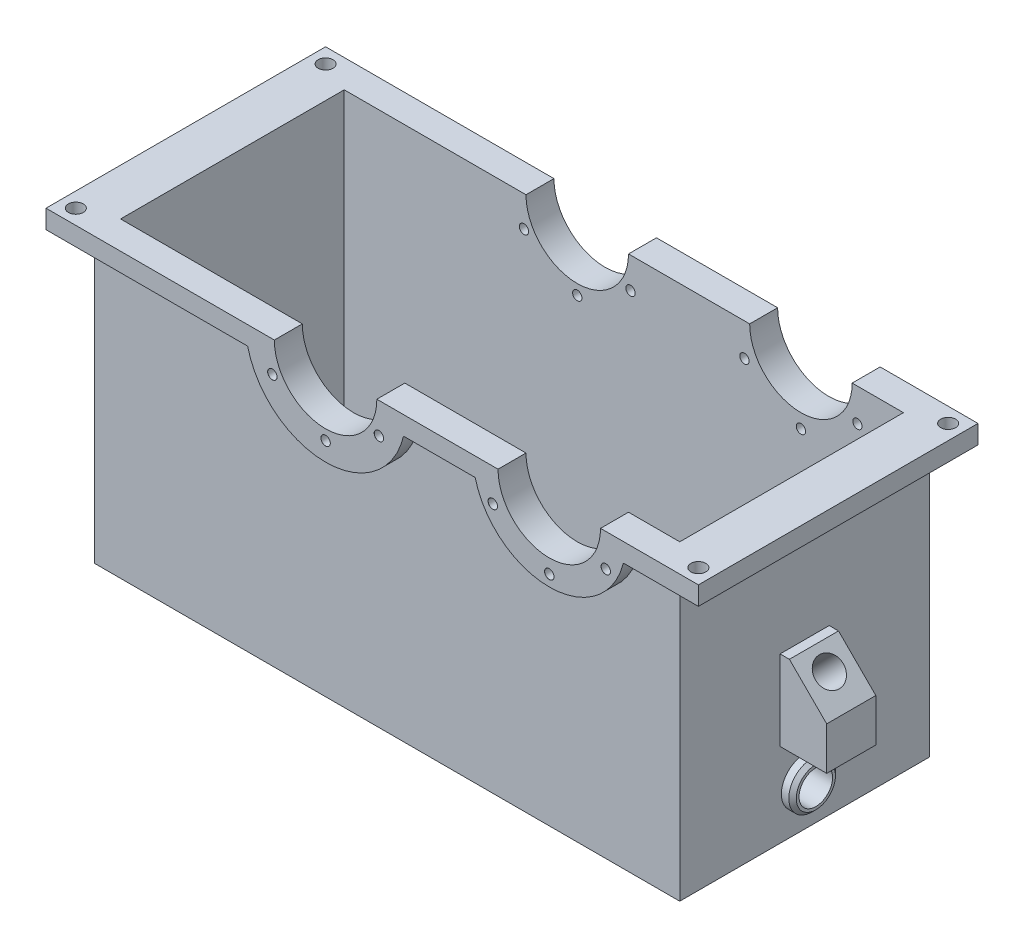
SolidWorks part; units mm, degrees
ref_plane "Front Plane" through (0, 0, 0) normal (0, 0, 1) x (1, 0, 0)
ref_plane "Top Plane" through (0, 0, 0) normal (0, 1, 0) x (1, 0, 0)
ref_plane "Right Plane" through (0, 0, 0) normal (1, 0, 0) x (0, 0, -1)
sketch "Sketch1" plane through (0, 0, 0) normal (0, 1, 0) x (1, 0, 0)
  line L1 (157, -67) -> (-157, -67)
  line L2 (157, -67) -> (157, 67)
  line L3 (157, 67) -> (-157, 67)
  line L4 (-157, -67) -> (-157, 67)
  line L5 (157, -67) -> (-157, 67) construction
  line L6 (157, 67) -> (-157, -67) construction
  point P0 (0, 0)
  dimension "D1" = 314
  dimension "D2" = 134
extrude "Boss-Extrude1" add sketch "Sketch1" along normal blind 160
sketch "Sketch2" plane through (0, 160, 0) normal (0, 1, 0) x (1, 0, 0)
  line L1 (175, -75) -> (-175, -75)
  line L2 (175, -75) -> (175, 75)
  line L3 (175, 75) -> (-175, 75)
  line L4 (-175, -75) -> (-175, 75)
  line L5 (175, -75) -> (-175, 75) construction
  line L6 (175, 75) -> (-175, -75) construction
  point P0 (0, 0)
  dimension "D1" = 350
  dimension "D2" = 150
extrude "Boss-Extrude3" add sketch "Sketch2" against normal blind 10
sketch "Sketch3" plane through (0, 0, 75) normal (0, 0, 1) x (1, 0, 0)
  line L0 (-175, 160) -> (175, 160) construction
  circle A0 centre (95, 160) radius 41
  circle A1 centre (95, 160) radius 27.5
  circle A2 centre (95, 160) radius 35 construction
  dimension "D2" = 82
  dimension "D3" = 55
  dimension "D4" = 70
  dimension "D1" = 80
extrude "Boss-Extrude5" add sketch "Sketch3" against normal through all contours A0
hole_wizard "Ø5.0mm Dowel Hole1" positions "Sketch4" profile "Sketch5" hole size "Ø5.0" standard "GB" end condition through all
sketch "Sketch4" plane through (0, 0, 75) normal (0, 0, 1) x (1, 0, 0)
  circle A0 centre (95, 160) radius 35 construction
  point P0 (95, 195)
sketch "Sketch5" plane through (95, 195, 75) normal (1, 0, 0) x (0, -1, 0)
  line L0 (0, 0) -> (0, 150)
  line L1 (0, 150) -> (2.5, 150)
  line L2 (2.5, 150) -> (2.5, 0.021)
  line L3 (2.5, 0.021) -> (2.525, 0)
  line L5 (2.525, 0) -> (0, 0)
  line L6 (-2.5, 0.021) -> (-2.525, 0) construction
  line L11 (0, -6.35) -> (0, 107.95) construction
  dimension "Thru Hole Dia." = 5
  dimension "Thru Hole Depth" = 150
  dimension "Near C'Sink Dia." = 5.05
  dimension "Near C'Sink Angle" = 100
pattern_circular "CirPattern1" count 6 over 360 about axis through (95, 160, -75) along (0, 0, 1) of "Ø5.0mm Dowel Hole1" reverse direction yes
extrude "Cut-Extrude1" cut sketch "Sketch3<3>" against normal through all contours A1
sketch "Sketch3<3>" plane through (0, 0, 75) normal (0, 0, 1) x (1, 0, 0) same geometry as "Sketch3"
sketch "Sketch6" plane through (0, 0, 75) normal (0, 0, 1) x (1, 0, 0)
  line L0 (-175, 160) -> (54, 160) construction
  circle A0 centre (-25, 160) radius 43
  circle A1 centre (-25, 160) radius 33 construction
  circle A2 centre (-25, 160) radius 27.5
  dimension "D2" = 86
  dimension "D3" = 55
  dimension "D4" = 66
  dimension "D1" = 120
extrude "Boss-Extrude6" add sketch "Sketch6" against normal through all contours A0
extrude "Cut-Extrude2" cut sketch "Sketch6<3>" against normal through all contours A2
sketch "Sketch6<3>" plane through (0, 0, 75) normal (0, 0, 1) x (1, 0, 0) same geometry as "Sketch6"
hole_wizard "Ø5.0mm Dowel Hole2" positions "Sketch7" profile "Sketch8" hole size "Ø5.0" standard "GB" end condition through all
sketch "Sketch7" plane through (0, 0, 75) normal (0, 0, 1) x (1, 0, 0)
  circle A0 centre (-25, 160) radius 33 construction
  point P0 (-25, 193)
sketch "Sketch8" plane through (-25, 193, 75) normal (1, 0, 0) x (0, -1, 0)
  line L0 (0, 0) -> (0, 150)
  line L1 (0, 150) -> (2.5, 150)
  line L2 (2.5, 150) -> (2.5, 0.021)
  line L3 (2.5, 0.021) -> (2.525, 0)
  line L5 (2.525, 0) -> (0, 0)
  line L6 (-2.5, 0.021) -> (-2.525, 0) construction
  line L11 (0, -6.35) -> (0, 107.95) construction
  dimension "Thru Hole Dia." = 5
  dimension "Thru Hole Depth" = 150
  dimension "Near C'Sink Dia." = 5.05
  dimension "Near C'Sink Angle" = 100
pattern_circular "CirPattern2" count 6 over 360 about axis through (-25, 160, -75) along (0, 0, 1) of "Ø5.0mm Dowel Hole2" reverse direction yes
mirror "Mirror1" about plane through (0, 0, 0) normal (0, 0, 1) of "CirPattern2"
mirror "Mirror2" about plane through (0, 0, 0) normal (0, 0, 1) of "CirPattern1"
sketch "Sketch9" plane through (157, 0, 0) normal (1, 0, 0) x (0, 0, -1)
  circle A0 centre (0, 22.5) radius 12.5
  circle A1 centre (0, 22.5) radius 9
  dimension "D2" = 25
  dimension "D3" = 18
  dimension "D1" = 22.5
extrude "Boss-Extrude7" add sketch "Sketch9" along normal blind 6 contours A0
extrude "Cut-Extrude3" cut sketch "Sketch9<3>" against normal blind 30 from offset 6 contours A1
sketch "Sketch9<3>" plane through (157, 0, 0) normal (1, 0, 0) x (0, 0, -1) same geometry as "Sketch9"
chamfer "Chamfer1" distance 2 angle 45 1 edges at (163, 22.5, -12.5)
sketch "Sketch10" plane through (157, 0, 0) normal (1, 0, 0) x (0, 0, -1)
  line L0 (0, 0) -> (0, 81.1635) construction
  line L1 (-13.175, 88) -> (13.175, 88)
  line L2 (-13.175, 88) -> (-13.175, 45)
  line L3 (-13.175, 45) -> (13.175, 45)
  line L4 (13.175, 88) -> (13.175, 45)
  line L5 (-67, 0) -> (67, 0) construction
  dimension "D1" = 45
  dimension "D2" = 43
  dimension "D3" = 26.35
extrude "Boss-Extrude8" add sketch "Sketch10" along normal blind 25
sketch "Sketch11" plane through (0, 0, -13.175) normal (0, 0, -1) x (-1, 0, 0)
  line L0 (-162, 88) -> (-182, 68)
  line L1 (-182, 88) -> (-157, 88) construction
  line L2 (-182, 45) -> (-182, 88) construction
  line L3 (-182, 45) -> (-157, 45) construction
  line L4 (-162, 88) -> (-183.7417, 106.3377)
  line L5 (-183.7417, 106.3377) -> (-200.6491, 72.8193)
  line L6 (-200.6491, 72.8193) -> (-182, 68)
  dimension "D1" = 5
  dimension "D2" = 23
extrude "Cut-Extrude4" cut sketch "Sketch11" against normal up to next
sketch "Sketch12" plane through (125, 125, 0) normal (0.7071, 0.7071, 0) x (0, 0, -1)
  circle A0 centre (0, -63.9932) radius 7.5
  dimension "D1" = 15
extrude "Cut-Extrude5" cut sketch "Sketch12" against normal blind 50
sketch "Sketch13" plane through (0, 160, 0) normal (0, 1, 0) x (1, 0, 0)
  line L0 (-175, 75) -> (-175, -75) construction
  line L1 (-68, 75) -> (-175, 75) construction
  circle A0 centre (-167, 67) radius 4
  dimension "D1" = 8
  dimension "D2" = 8
  dimension "D3" = 8
extrude "Cut-Extrude6" cut sketch "Sketch13" against normal through all both and the other way through all
mirror "Mirror3" about plane through (0, 0, 0) normal (1, 0, 0) of "Cut-Extrude6"
mirror "Mirror4" about plane through (0, 0, 0) normal (0, 0, 1) of "Cut-Extrude6"
mirror "Mirror5" about plane through (0, 0, 0) normal (0, 0, 1) of "Mirror3"
sketch "Sketch14" plane through (0, 0, 75) normal (0, 0, 1) x (1, 0, 0)
  line L1 (-175, 160) -> (189.1664, 160)
  line L2 (-175, 160) -> (-175, 252.8203)
  line L3 (-175, 252.8203) -> (189.1664, 252.8203)
  line L4 (189.1664, 160) -> (189.1664, 252.8203)
extrude "Cut-Extrude7" cut sketch "Sketch14" against normal through all
sketch "Sketch15" plane through (0, 160, 0) normal (0, 1, 0) x (1, 0, 0)
  line L1 (150, -60) -> (-150, -60)
  line L2 (150, -60) -> (150, 60)
  line L3 (150, 60) -> (-150, 60)
  line L4 (-150, -60) -> (-150, 60)
  line L5 (150, -60) -> (-150, 60) construction
  line L6 (150, 60) -> (-150, -60) construction
  point P0 (0, 0)
  dimension "D1" = 300
  dimension "D2" = 120
extrude "Cut-Extrude9" cut sketch "Sketch15" against normal offset from surface (150 mm away) 10 up to face at (0, 0, 0)
